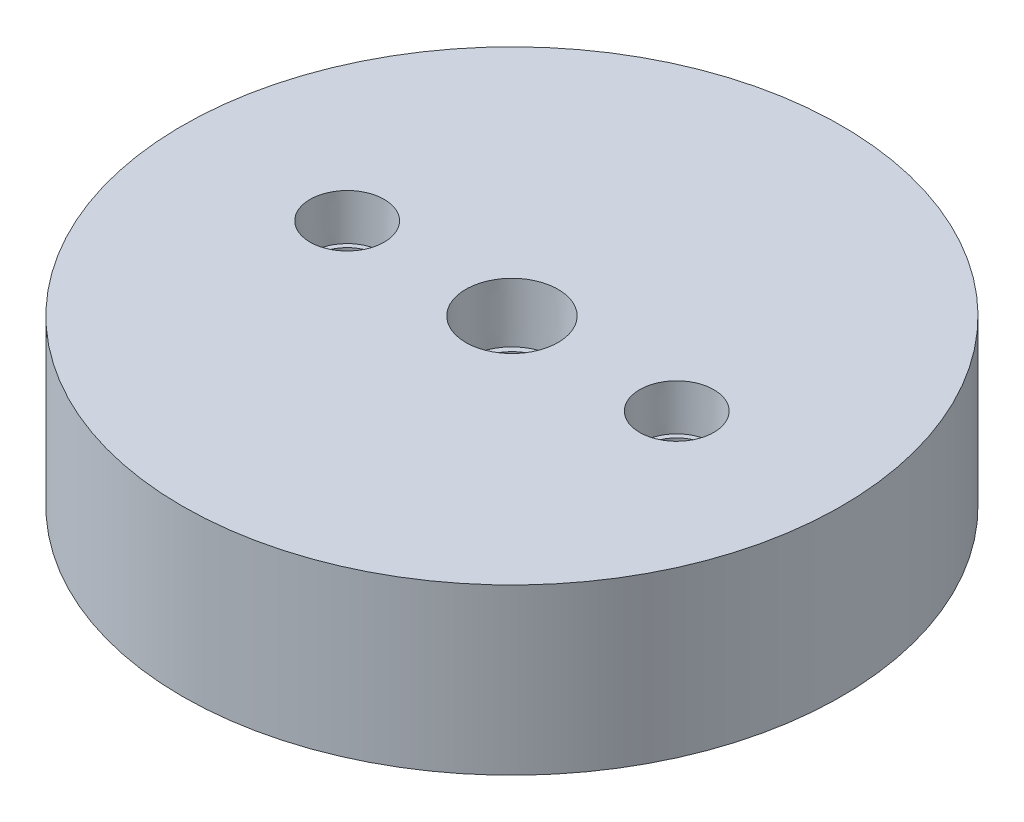
SolidWorks part; units mm, degrees
ref_plane "Front Plane" through (0, 0, 0) normal (0, 0, 1) x (1, 0, 0)
ref_plane "Top Plane" through (0, 0, 0) normal (0, 1, 0) x (1, 0, 0)
ref_plane "Right Plane" through (0, 0, 0) normal (1, 0, 0) x (0, 0, -1)
ref_axis "Axial" through (0, 53.34, 0) along (0, -1, 0)
ref_plane "Bottom Plane" through (0, -50.8, 0) normal (0, 1, 0) x (1, 0, 0)
sketch "Sketch1" plane through (0, 0, 0) normal (0, 1, 0) x (1, 0, 0)
  circle A0 centre (0, 0) radius 76.2
  dimension "D1" = 152.4
extrude "Billet" add sketch "Sketch1" against normal blind 50.8
sketch "Sketch3" plane through (0, -50.8, 0) normal (0, 1, 0) x (1, 0, 0)
  line L0 (0, 81.5114) -> (0, -83.2162) construction
  circle A0 centre (0, 0) radius 28.575
  dimension "D1" = 57.15
  dimension "D2" = 0
extrude "Lox Plate" cut sketch "Sketch3" along normal blind 17.78
sketch "Sketch5" plane through (0, -33.02, 0) normal (0, 1, 0) x (1, 0, 0)
  line L0 (0, 57.2178) -> (0, -49.9723) construction
  circle A0 centre (0, 0) radius 22.225
  dimension "D1" = 44.45
  dimension "D2" = 0
extrude "Lox Dome" cut sketch "Sketch5" along normal blind 4.4628
sketch "Sketch7" plane through (0, 0, 0) normal (0, 1, 0) x (1, 0, 0)
  circle A1 centre (0, 0) radius 76.2
  dimension "D2" = 152.4
extrude "Top Mill" cut sketch "Sketch7" against normal blind 12.7
sketch "Sketch11" plane through (0, -50.8, 0) normal (0, 1, 0) x (1, 0, 0)
  line L0 (0, 82.3071) -> (0, -82.946) construction
  circle A0 centre (0, 68.58) radius 3.175
  dimension "D1" = 6.35
  dimension "D2" = 68.58
sketch "Sketch12" plane through (0, -50.8, 0) normal (0, 1, 0) x (1, 0, 0)
  circle A0 centre (0, 0) radius 60.96
  dimension "D1" = 121.92
extrude "Kerosene Plate" cut sketch "Sketch12" along normal blind 12.7
hole_wizard "Lox Inlet-1/2 NPT Tapped Hole3" positions "Sketch20" profile "Sketch21" size "1/2" standard "ANSI Inch" end condition through all
sketch "Sketch20" plane through (0, -12.7, 0) normal (0, 1, 0) x (1, 0, 0)
  line L0 (0, 40.1697) -> (0, -38.6779) construction
  point P8 (0, 0)
  dimension "D1" = 0
sketch "Sketch21" plane through (0, -12.7, 0) normal (1, 0, 0) x (0, 0, 1)
  line L0 (0, 0) -> (0, 38.1)
  line L1 (0, 38.1) -> (8.9281, 38.1)
  line L2 (-10.2617, 13.462) -> (-10.6647, 0) construction
  line L3 (8.9281, 38.1) -> (8.9281, 13.462)
  line L4 (8.9281, 13.462) -> (10.2617, 13.462)
  line L5 (10.2617, 13.462) -> (10.6647, 0)
  line L7 (10.6647, 0) -> (0, 0)
  line L8 (0, -6.35) -> (0, 107.95) construction
  line L11 (-8.9281, 13.462) -> (-10.2617, 13.462) construction
  dimension "Thru Tap Drill Dia." = 17.8562
  dimension "Thru Tap Drill Depth" = 38.1
  dimension "Thread Dia." = 21.3295
  dimension "Thread Angle" = 3.43
  dimension "Thread Depth" = 13.462
hole_wizard "Kerosene Inlet-3/8 NPT Tapped Hole1" positions "Sketch24" profile "Sketch25" size "3/8" standard "ANSI Inch" end condition through all
sketch "Sketch24" plane through (0, -12.7, 0) normal (0, 1, 0) x (1, 0, 0)
  point P0 (-38.1, 0)
  point P2 (38.1, 0)
  dimension "D1" = 38.1
  dimension "D2" = 38.1
sketch "Sketch25" plane through (-38.1, -12.7, 0) normal (1, 0, 0) x (0, 0, 1)
  line L0 (0, 0) -> (0, 38.1)
  line L1 (0, 38.1) -> (7.1374, 38.1)
  line L2 (-8.2632, 10.414) -> (-8.575, 0) construction
  line L3 (7.1374, 38.1) -> (7.1374, 10.414)
  line L4 (7.1374, 10.414) -> (8.2632, 10.414)
  line L5 (8.2632, 10.414) -> (8.575, 0)
  line L7 (8.575, 0) -> (0, 0)
  line L8 (0, -6.35) -> (0, 107.95) construction
  line L11 (-7.1374, 10.414) -> (-8.2632, 10.414) construction
  dimension "Thru Tap Drill Dia." = 14.2748
  dimension "Thru Tap Drill Depth" = 38.1
  dimension "Thread Dia." = 17.15
  dimension "Thread Angle" = 3.43
  dimension "Thread Depth" = 10.414
sketch "Sketch27" plane through (0, -38.1, 0) normal (0, -1, 0) x (1, 0, 0)
  line L0 (0, 82.1632) -> (0, -90.1459) construction
  line L1 (20.955, 0) -> (-20.955, 0) construction
  circle A0 centre (0, 50.8) radius 1.1906
  circle A1 centre (0, -50.8) radius 1.1906
  dimension "D1" = 2.3813
  dimension "D2" = 50.8
